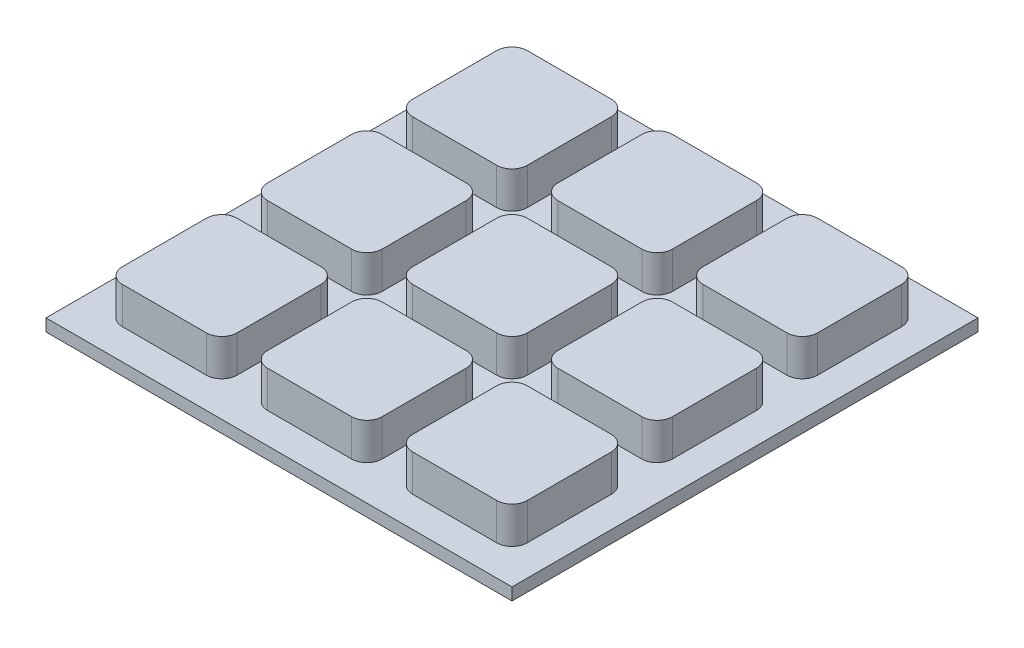
SolidWorks part; units mm, degrees
ref_plane "Front Plane" through (0, 0, 0) normal (0, 0, 1) x (1, 0, 0)
ref_plane "Top Plane" through (0, 0, 0) normal (0, 1, 0) x (1, 0, 0)
ref_plane "Right Plane" through (0, 0, 0) normal (1, 0, 0) x (0, 0, -1)
sketch "Sketch1" plane through (0, 0, 0) normal (0, 1, 0) x (1, 0, 0)
  line L1 (30.5, -30.5) -> (-30.5, -30.5)
  line L2 (30.5, -30.5) -> (30.5, 30.5)
  line L3 (30.5, 30.5) -> (-30.5, 30.5)
  line L4 (-30.5, -30.5) -> (-30.5, 30.5)
  line L5 (30.5, -30.5) -> (-30.5, 30.5) construction
  line L6 (30.5, 30.5) -> (-30.5, -30.5) construction
  point P0 (0, 0)
  dimension "D1" = 61
  dimension "D2" = 61
extrude "Boss-Extrude1" add sketch "Sketch1" along normal blind 1.6
sketch "Sketch2" plane through (0, 1.6, 0) normal (0, 1, 0) x (1, 0, 0)
  line L1 (-26.5, 26.5) -> (-11.5, 26.5)
  line L2 (-26.5, 26.5) -> (-26.5, 11.5)
  line L3 (-26.5, 11.5) -> (-11.5, 11.5)
  line L4 (-11.5, 26.5) -> (-11.5, 11.5)
  line L5 (-26.5, 26.5) -> (-11.5, 11.5) construction
  line L6 (-26.5, 11.5) -> (-11.5, 26.5) construction
  line L7 (-7.5, 26.5) -> (7.5, 26.5)
  line L8 (-7.5, 26.5) -> (-7.5, 11.5)
  line L9 (-7.5, 11.5) -> (7.5, 11.5)
  line L10 (7.5, 26.5) -> (7.5, 11.5)
  line L11 (-7.5, 26.5) -> (7.5, 11.5) construction
  line L12 (-7.5, 11.5) -> (7.5, 26.5) construction
  line L13 (11.5, 26.5) -> (26.5, 26.5)
  line L14 (11.5, 26.5) -> (11.5, 11.5)
  line L15 (11.5, 11.5) -> (26.5, 11.5)
  line L16 (26.5, 26.5) -> (26.5, 11.5)
  line L17 (11.5, 26.5) -> (26.5, 11.5) construction
  line L18 (11.5, 11.5) -> (26.5, 26.5) construction
  line L19 (11.5, 7.5) -> (26.5, 7.5)
  line L20 (11.5, 7.5) -> (11.5, -7.5)
  line L21 (11.5, -7.5) -> (26.5, -7.5)
  line L22 (26.5, 7.5) -> (26.5, -7.5)
  line L23 (11.5, 7.5) -> (26.5, -7.5) construction
  line L24 (11.5, -7.5) -> (26.5, 7.5) construction
  line L25 (-7.5, 7.5) -> (7.5, 7.5)
  line L26 (-7.5, 7.5) -> (-7.5, -7.5)
  line L27 (-7.5, -7.5) -> (7.5, -7.5)
  line L28 (7.5, 7.5) -> (7.5, -7.5)
  line L29 (-7.5, 7.5) -> (7.5, -7.5) construction
  line L30 (-7.5, -7.5) -> (7.5, 7.5) construction
  line L31 (-26.5, 7.5) -> (-11.5, 7.5)
  line L32 (-26.5, 7.5) -> (-26.5, -7.5)
  line L33 (-26.5, -7.5) -> (-11.5, -7.5)
  line L34 (-11.5, 7.5) -> (-11.5, -7.5)
  line L35 (-26.5, 7.5) -> (-11.5, -7.5) construction
  line L36 (-26.5, -7.5) -> (-11.5, 7.5) construction
  line L37 (-26.5, -11.5) -> (-11.5, -11.5)
  line L38 (-26.5, -11.5) -> (-26.5, -26.5)
  line L39 (-26.5, -26.5) -> (-11.5, -26.5)
  line L40 (-11.5, -11.5) -> (-11.5, -26.5)
  line L41 (-26.5, -11.5) -> (-11.5, -26.5) construction
  line L42 (-26.5, -26.5) -> (-11.5, -11.5) construction
  line L43 (-7.5, -11.5) -> (7.5, -11.5)
  line L44 (-7.5, -11.5) -> (-7.5, -26.5)
  line L45 (-7.5, -26.5) -> (7.5, -26.5)
  line L46 (7.5, -11.5) -> (7.5, -26.5)
  line L47 (-7.5, -11.5) -> (7.5, -26.5) construction
  line L48 (-7.5, -26.5) -> (7.5, -11.5) construction
  line L49 (11.5, -11.5) -> (26.5, -11.5)
  line L50 (11.5, -11.5) -> (11.5, -26.5)
  line L51 (11.5, -26.5) -> (26.5, -26.5)
  line L52 (26.5, -11.5) -> (26.5, -26.5)
  line L53 (11.5, -11.5) -> (26.5, -26.5) construction
  line L54 (11.5, -26.5) -> (26.5, -11.5) construction
  point P0 (-19, 19)
  point P5 (0, 19)
  point P10 (19, 19)
  point P15 (19, 0)
  point P20 (0, 0)
  point P25 (-19, 0)
  point P30 (-19, -19)
  point P35 (0, -19)
  point P40 (19, -19)
  dimension "D1" = 15
  dimension "D2" = 4
  dimension "D3" = 4
  dimension "D4" = 4
  dimension "D5" = 4
extrude "Boss-Extrude2" add sketch "Sketch2" along normal blind 4.8
fillet "Fillet1" radius 2 36 edges at (26.5, 4, -11.5) (26.5, 4, -26.5) (11.5, 4, -26.5) (11.5, 4, -11.5) (-7.5, 4, -11.5) (7.5, 4, -11.5) (7.5, 4, -26.5) (-7.5, 4, -26.5) (-26.5, 4, -26.5) (-11.5, 4, -26.5) (-11.5, 4, -11.5) (-26.5, 4, -11.5) (-11.5, 4, 11.5) (-11.5, 4, 26.5) (-26.5, 4, 26.5) (-26.5, 4, 11.5) (-7.5, 4, 11.5) (-7.5, 4, 26.5) (7.5, 4, 11.5) (7.5, 4, 26.5) (26.5, 4, 26.5) (11.5, 4, 26.5) (11.5, 4, 11.5) (26.5, 4, 11.5) (11.5, 4, -7.5) (26.5, 4, -7.5) (26.5, 4, 7.5) (11.5, 4, 7.5) (7.5, 4, 7.5) (7.5, 4, -7.5) (-7.5, 4, 7.5) (-7.5, 4, -7.5) (-26.5, 4, -7.5) (-11.5, 4, -7.5) (-11.5, 4, 7.5) (-26.5, 4, 7.5)
